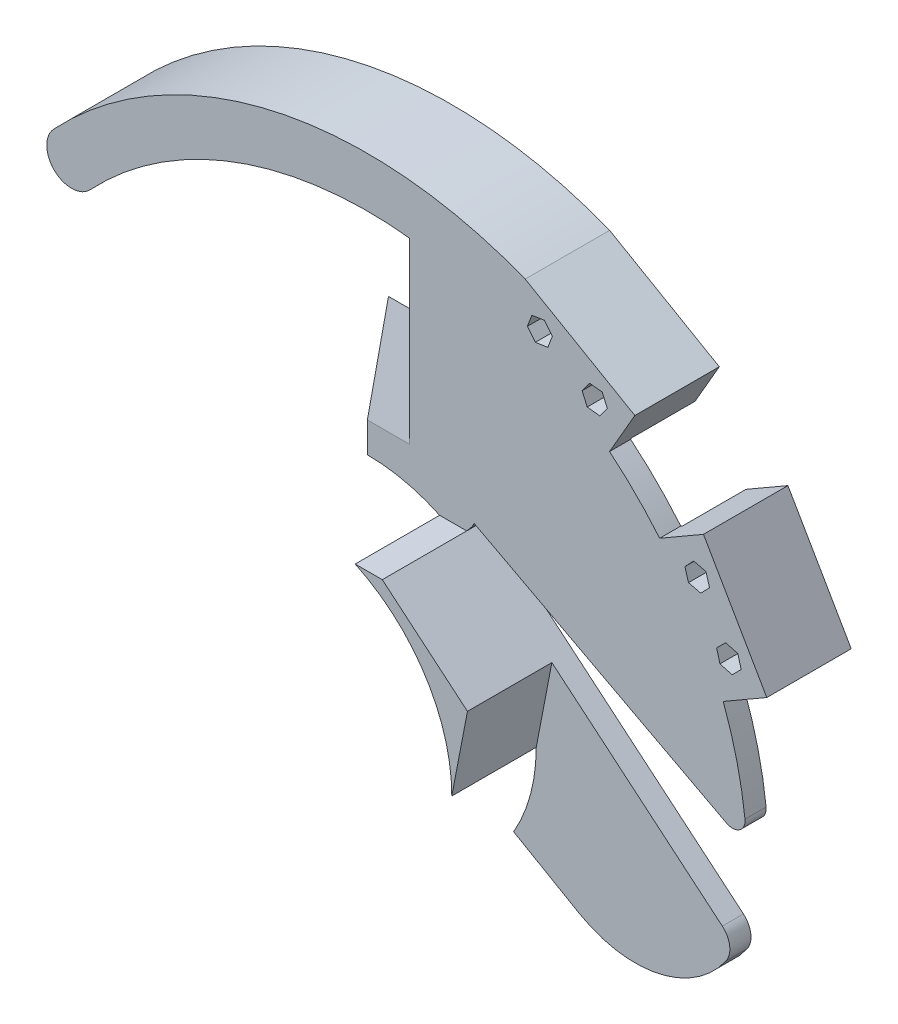
SolidWorks part; units mm, degrees
ref_plane "Front Plane" through (0, 0, 0) normal (0, 0, 1) x (1, 0, 0)
ref_plane "Top Plane" through (0, 0, 0) normal (0, 1, 0) x (1, 0, 0)
ref_plane "Right Plane" through (0, 0, 0) normal (1, 0, 0) x (0, 0, -1)
sketch "Sketch1" plane through (0, 0, 0) normal (0, 0, 1) x (1, 0, 0)
  line L0 (0, 0) -> (0, 90)
  line L1 (0, 0) -> (50.2261, -28.9981)
  line L2 (0, 0) -> (164.7219, 0) construction
  line L3 (10, 89.4427) -> (10, 70)
  line L4 (10, 70) -> (0, 70)
  line L5 (0, 70) -> (0, 0)
  circle A0 centre (0, 0) radius 90
  circle A1 centre (0, 0) radius 40
  arc A2 (50.2261, -28.9981) -> (89.765, -6.4991) centre (63.4065, -6.1691) ccw
  dimension "D1" = 180
  dimension "D2" = 80
  dimension "D5" = 26.3606
  dimension "D7" = 63.4065
  dimension "D8" = 50
  dimension "D3" = 120
  dimension "D4" = 90
  dimension "D6" = 10
  dimension "D9" = 70
extrude "Boss-Extrude1" add sketch "Sketch1" against normal blind 5 contours A1 L2 A0 L0 | L2 A1 L1 A2 A0 region at (44.9731, 41.9474, 0) region at (63.1952, -14.4217, 0)
sketch "Sketch2" plane through (0, 0, 0) normal (0, 0, 1) x (1, 0, 0)
  circle A0 centre (0, 0) radius 40
sketch "Sketch3" plane through (0, 0, 0) normal (1, 0, 0) x (0, 0, -1)
  line L0 (22.9492, 0) -> (-22.3506, 0) construction
sketch "Sketch10" plane through (0, 0, 0) normal (-1, 0, 0) x (0, 0, 1)
  line L0 (-5, 70) -> (0, 47.1666)
  line L2 (0, 40) -> (0, 70) construction
  line L3 (0, 47.1666) -> (0, 70)
  line L4 (0, 70) -> (-5, 70)
extrude "Cut-Extrude1" cut sketch "Sketch10" against normal blind 10
sketch "Sketch13" plane through (0, 0, 0) normal (0, 0, 1) x (1, 0, 0)
  line L0 (0, 0) -> (62.2768, 107.8665) construction
  line L1 (0, 0) -> (111.0381, 0) construction
  line L2 (31.3802, 84.3521) -> (37.3802, 94.7444)
  line L3 (37.3802, 94.7444) -> (63.361, 79.7444)
  line L4 (63.361, 79.7444) -> (57.361, 69.3521)
  line L5 (-0.1063, 0.0266) -> (91.5093, 91.6422) construction
  line L6 (79.6115, 63.4939) -> (69.2192, 57.4939)
  line L7 (94.6115, 37.5131) -> (79.6115, 63.4939)
  line L8 (84.2192, 31.5131) -> (94.6115, 37.5131)
  line L9 (10, 47.1666) -> (0, 47.1666)
  line L10 (0, 47.1666) -> (0, 40)
  line L11 (34.641, -20) -> (50.2261, -28.9981)
  line L12 (10, 89.4427) -> (10, 47.1666)
  line L13 (10, 47.1666) -> (0, 47.1666)
  line L14 (0, 47.1666) -> (0, 40)
  line L15 (34.641, -20) -> (50.2261, -28.9981)
  line L16 (10, 89.4427) -> (10, 47.1666)
  arc A0 (89.3343, -10.9263) -> (10, 89.4427) centre (0, 0) ccw construction
  circle A1 centre (40.8566, 85.7656) radius 2.5
  circle A2 centre (53.8469, 78.2656) radius 2.5
  circle A3 centre (0, 0) radius 95 construction
  circle A4 centre (78.1327, 53.9798) radius 2.5
  circle A5 centre (85.6327, 40.9895) radius 2.5
  arc A7 (34.641, -20) -> (0, 40) centre (0, 0) ccw
  arc A8 (50.2261, -28.9981) -> (89.3343, -10.9263) centre (63.4065, -6.1691) ccw
  arc A9 (89.3343, -10.9263) -> (10, 89.4427) centre (0, 0) ccw
  arc A10 (34.641, -20) -> (0, 40) centre (0, 0) ccw
  arc A11 (50.2261, -28.9981) -> (89.3343, -10.9263) centre (63.4065, -6.1691) ccw
  arc A12 (89.3343, -10.9263) -> (10, 89.4427) centre (0, 0) ccw
  dimension "D5" = 190
  dimension "D6" = 5
  dimension "D7" = 5
  dimension "D8" = 7.5
  dimension "D9" = 7.5
  dimension "D1" = 60
  dimension "D2" = 30
  dimension "D3" = 15
  dimension "D4" = 12
  dimension "D11" = 45
  dimension "D10" = 0
extrude "Boss-Extrude3" add sketch "Sketch13" along normal up to surface from offset 3 contours A12 L4 L3 L2 A2 A1 | A12 L8 L7 L6 A4 A5 region at (47.6076, 82.4587, 0) region at (82.342, 47.7678, 0) up to face at (33.8779, 25.7524, 0) offset against normal yes
chamfer "Chamfer1" distance 2 angle 45 1 edges at (45, 77.9423, -3)
sketch "Sketch21" plane through (0, 0, -3) normal (0, 0, -1) x (-1, 0, 0)
  line L0 (-32.3941, 86.1082) -> (-37.3802, 94.7444)
  line L1 (-37.3802, 94.7444) -> (-63.361, 79.7444)
  line L2 (-63.361, 79.7444) -> (-58.3748, 71.1082)
  line L3 (-86.0433, 32.5662) -> (-94.6115, 37.5131)
  line L4 (-94.6115, 37.5131) -> (-79.6115, 63.4939)
  line L5 (-79.6115, 63.4939) -> (-70.9913, 58.517)
  arc A0 (-70.9913, 58.517) -> (-86.0433, 32.5662) centre (0, 0) ccw
  arc A1 (-32.3941, 86.1082) -> (-58.3748, 71.1082) centre (0, 0) ccw
extrude "Boss-Extrude7" add sketch "Sketch21" along normal up to surface (17 mm away)
sketch "Sketch22" plane through (0, 0, 0) normal (0, 0, 1) x (1, 0, 0)
  circle A0 centre (40.8566, 85.7656) radius 1.6
  circle A1 centre (53.8469, 78.2656) radius 1.6
  circle A2 centre (78.1327, 53.9798) radius 1.6
  circle A3 centre (85.6327, 40.9895) radius 1.6
  dimension "D1" = 3.2
  dimension "D2" = 3.2
  dimension "D3" = 3.2
  dimension "D4" = 3.2
extrude "Cut-Extrude4" cut sketch "Sketch22" against normal up to surface (20 mm away) up to face at (48.0314, 83.1929, -20)
sketch "Sketch24" plane through (0, 0, 0) normal (0, 0, 1) x (1, 0, 0)
  line L1 (42.7415, 83.4289) -> (43.8227, 86.2296)
  line L2 (43.8227, 86.2296) -> (41.9378, 88.5664)
  line L3 (41.9378, 88.5664) -> (38.9716, 88.1024)
  line L4 (38.9716, 88.1024) -> (37.8904, 85.3016)
  line L5 (37.8904, 85.3016) -> (39.7753, 82.9649)
  line L6 (39.7753, 82.9649) -> (42.7415, 83.4289)
  line L7 (55.059, 75.519) -> (56.8317, 77.942)
  line L8 (56.8317, 77.942) -> (55.6196, 80.6887)
  line L9 (55.6196, 80.6887) -> (52.6348, 81.0123)
  line L10 (52.6348, 81.0123) -> (50.8622, 78.5892)
  line L11 (50.8622, 78.5892) -> (52.0743, 75.8426)
  line L12 (52.0743, 75.8426) -> (55.059, 75.519)
  line L13 (78.9769, 51.0987) -> (81.0499, 53.2704)
  line L14 (81.0499, 53.2704) -> (80.2057, 56.1515)
  line L15 (80.2057, 56.1515) -> (77.2885, 56.8609)
  line L16 (77.2885, 56.8609) -> (75.2155, 54.6893)
  line L17 (75.2155, 54.6893) -> (76.0597, 51.8082)
  line L18 (76.0597, 51.8082) -> (78.9769, 51.0987)
  line L19 (86.4099, 38.0896) -> (88.5327, 40.2126)
  line L20 (88.5327, 40.2126) -> (87.7555, 43.1125)
  line L21 (87.7555, 43.1125) -> (84.8555, 43.8893)
  line L22 (84.8555, 43.8893) -> (82.7328, 41.7663)
  line L23 (82.7328, 41.7663) -> (83.5099, 38.8665)
  line L24 (83.5099, 38.8665) -> (86.4099, 38.0896)
  circle A0 centre (40.8566, 85.7656) radius 2.6 construction
  circle A1 centre (53.8469, 78.2656) radius 2.6 construction
  circle A2 centre (78.1327, 53.9798) radius 2.6 construction
  circle A3 centre (85.6327, 40.9895) radius 2.6 construction
  dimension "D1" = 5.2
extrude "Cut-Extrude5" cut sketch "Sketch24" against normal blind 7
sketch "Sketch25" plane through (0, 0, -20) normal (0, 0, -1) x (-1, 0, 0)
  line L0 (-86.0433, 32.5662) -> (-84.2878, 31.5527)
  line L1 (-70.9913, 58.517) -> (-69.2346, 57.5028)
  line L2 (-58.3748, 71.1082) -> (-57.361, 69.3521)
  line L3 (-32.3941, 86.1082) -> (-31.3802, 84.3521)
  arc A0 (-69.2346, 57.5028) -> (-84.2878, 31.5527) centre (0, 0) ccw
  arc A1 (-70.9913, 58.517) -> (-86.0433, 32.5662) centre (0, 0) ccw
  arc A2 (-32.3941, 86.1082) -> (-58.3748, 71.1082) centre (0, 0) ccw
  arc A3 (-31.3802, 84.3521) -> (-57.361, 69.3521) centre (0, 0) ccw
extrude "Boss-Extrude8" add sketch "Sketch25" against normal up to surface (20 mm away) up to face at (40.8566, 85.7656, 0)
sketch "Sketch26" plane through (0, 0, -5) normal (0, 0, -1) x (-1, 0, 0)
  circle A0 centre (0, 0) radius 90
  circle A1 centre (0, 0) radius 90.5
  dimension "D1" = 180
  dimension "D2" = 181
extrude "Cut-Extrude6" cut sketch "Sketch26" along normal up to surface (15 mm away) up to face at (76.5327, 53.9798, -20)
sketch "Sketch28" plane through (0, 0, 0) normal (0, 0, 1) x (1, 0, 0)
  line L0 (23.5333, 36.1548) -> (43.7013, 19.2318)
  line L1 (43.7013, 19.2318) -> (40, 0)
  line L4 (17.1123, 36.1548) -> (23.5333, 36.1548)
  line L6 (-66.1454, 36.1548) -> (113.2119, 36.1548) construction
  arc A0 (34.641, -20) -> (0, 40) centre (0, 0) ccw construction
  arc A1 (40, 0) -> (17.1123, 36.1548) centre (0, 0) ccw
  point P2 (23.5333, 36.1548)
  dimension "D1" = 40
extrude "Boss-Extrude9" add sketch "Sketch28" along normal blind 20
sketch "Sketch30" plane through (0, 0, 0) normal (0, 0, 1) x (1, 0, 0)
  line L1 (31.3802, 84.3521) -> (37.3802, 94.7444)
  line L2 (-78.5366, 64.8521) -> (-69.3978, 57.3057)
  arc A0 (37.3802, 94.7444) -> (-78.5366, 64.8521) centre (0, 0) ccw
  arc A1 (31.3802, 84.3521) -> (-69.3978, 57.3057) centre (0, 0) ccw
extrude "Boss-Extrude11" add sketch "Sketch30" against normal up to surface (20 mm away) up to face at (39.2566, 85.7656, -20)
fillet "Fillet2" radius 6 2 edges at (-69.3978, 57.3057, -10) (-78.5366, 64.8521, -10)
ref_plane "Plane1" through (0, 0, 0) normal (0, 0, -1) x (-1, 0, 0)
sketch "Sketch31" plane through (0, 0, 0) normal (0, 0, -1) x (-1, 0, 0)
  line L7 (-126.5389, -27.9904) -> (-128.4205, -25.7479)
  line L8 (-128.4205, -25.7479) -> (-227.9002, -109.2212)
  line L9 (-227.9002, -109.2212) -> (-215.0444, -124.5421)
  line L10 (-215.0444, -124.5421) -> (-23.5333, 36.1548)
  line L11 (-23.5333, 36.1548) -> (-24.8189, 37.6869)
  line L12 (-24.8189, 37.6869) -> (-88.1305, 4.238)
  line L13 (-88.1305, 4.238) -> (-126.5389, -27.9904)
  line L14 (-126.5389, -27.9904) -> (-128.4205, -25.7479)
  line L15 (-128.4205, -25.7479) -> (-227.9002, -109.2212)
  line L16 (-227.9002, -109.2212) -> (-215.0444, -124.5421)
  line L17 (-215.0444, -124.5421) -> (-23.5333, 36.1548)
  line L18 (-23.5333, 36.1548) -> (-24.8189, 37.6869)
  line L19 (-24.8189, 37.6869) -> (-88.1305, 4.238)
  line L20 (-88.1305, 4.238) -> (-126.5389, -27.9904)
  dimension "D1" = 0
extrude "Cut-Extrude8" cut sketch "Sketch31" along normal blind 5
fillet "Fillet3" radius 5 1 edges at (87.2839, -17.3383, -2.5)
sketch "Sketch32" plane through (0, 0, 0) normal (0, 0, 1) x (1, 0, 0)
  line L0 (87.4655, 4.5893) -> (92.8099, 1.7658)
  line L1 (24.8189, 37.6869) -> (88.1305, 4.238) construction
  line L2 (92.8099, 1.7658) -> (89.6702, 2.2927)
  line L3 (89.6702, 2.2927) -> (87.4655, 4.5893)
extrude "Cut-Extrude9" cut sketch "Sketch32" against normal blind 5
fillet "Fillet4" radius 3 1 edges at (89.9401, 3.282, -2.5)
sketch "Sketch33" plane through (0, 0, 0) normal (0, 0, 1) x (1, 0, 0)
  line L0 (24.8189, 37.6869) -> (88.6014, 3.9892)
  line L1 (88.6014, 3.9892) -> (89.0686, 4.8734)
  line L2 (89.0686, 4.8734) -> (25.286, 38.5711)
  line L3 (25.286, 38.5711) -> (24.8189, 37.6869)
  dimension "D1" = 1
extrude "Cut-Extrude11" cut sketch "Sketch33" against normal blind 5
fillet "Fillet5" radius 3 1 edges at (87.632, 5.6324, -2.5)
